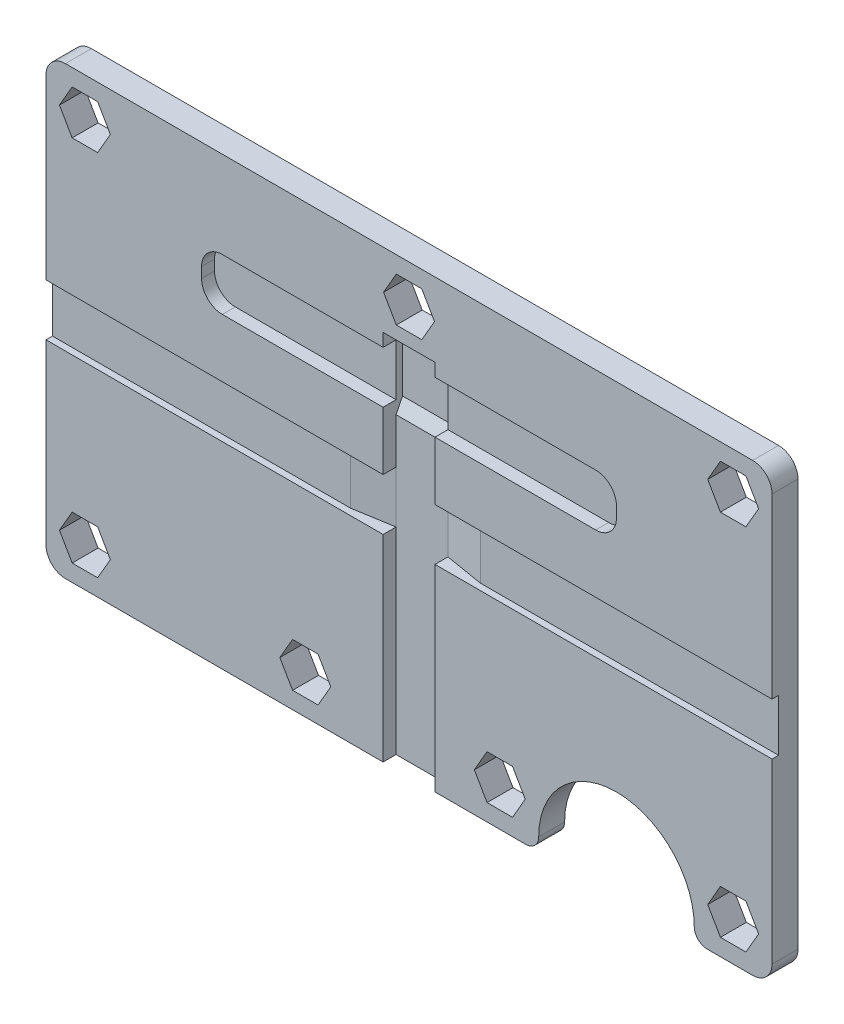
SolidWorks part; units mm, degrees
ref_plane "Front Plane" through (0, 0, 0) normal (0, 0, 1) x (1, 0, 0)
ref_plane "Top Plane" through (0, 0, 0) normal (0, 1, 0) x (1, 0, 0)
ref_plane "Right Plane" through (0, 0, 0) normal (1, 0, 0) x (0, 0, -1)
ref_plane "Plane1" through (0, 0, 1.6) normal (0, 0, 1) x (1, 0, 0)
sketch "Sketch1" plane through (0, 0, 1.6) normal (0, 0, 1) x (1, 0, 0)
  line L0 (-17.6412, 50.8492) -> (-17.6412, 1.0017)
  line L1 (-15.26, -1.3795) -> (41.0963, -1.3795)
  line L2 (63.3213, -1.3795) -> (68.8775, -1.3795)
  line L3 (71.2588, 1.0017) -> (71.2588, 50.8492)
  line L4 (68.8775, 53.2305) -> (-15.26, 53.2305)
  line L5 (26.8088, 53.1969) -> (26.8088, 50053.1969) construction
  line L6 (61.7338, 0.6891) -> (61.7338, -49999.3109) construction
  line L7 (-12.8787, 3.383) -> (37.9213, 3.383) construction
  line L15 (-9.761, 48.468) -> (-11.3199, 51.168)
  line L16 (-11.3199, 51.168) -> (-14.4376, 51.168)
  line L17 (-14.4376, 51.168) -> (-15.9964, 48.468)
  line L18 (-15.9964, 48.468) -> (-14.4376, 45.768)
  line L19 (-14.4376, 45.768) -> (-11.3199, 45.768)
  line L20 (-11.3199, 45.768) -> (-9.761, 48.468)
  line L21 (69.614, 3.383) -> (68.0551, 6.083)
  line L22 (68.0551, 6.083) -> (64.9374, 6.083)
  line L23 (64.9374, 6.083) -> (63.3786, 3.383)
  line L24 (63.3786, 3.383) -> (64.9374, 0.683)
  line L25 (64.9374, 0.683) -> (68.0551, 0.683)
  line L26 (68.0551, 0.683) -> (69.614, 3.383)
  line L27 (69.614, 48.468) -> (68.0551, 51.168)
  line L28 (68.0551, 51.168) -> (64.9374, 51.168)
  line L29 (64.9374, 51.168) -> (63.3786, 48.468)
  line L30 (63.3786, 48.468) -> (64.9374, 45.768)
  line L31 (64.9374, 45.768) -> (68.0551, 45.768)
  line L32 (68.0551, 45.768) -> (69.614, 48.468)
  line L33 (41.039, 3.383) -> (39.4801, 6.083)
  line L34 (39.4801, 6.083) -> (36.3624, 6.083)
  line L35 (36.3624, 6.083) -> (34.8036, 3.383)
  line L36 (34.8036, 3.383) -> (36.3624, 0.683)
  line L37 (36.3624, 0.683) -> (39.4801, 0.683)
  line L38 (39.4801, 0.683) -> (41.039, 3.383)
  line L39 (17.2265, 3.383) -> (15.6676, 6.083)
  line L40 (15.6676, 6.083) -> (12.5499, 6.083)
  line L41 (12.5499, 6.083) -> (10.9911, 3.383)
  line L42 (10.9911, 3.383) -> (12.5499, 0.683)
  line L43 (12.5499, 0.683) -> (15.6676, 0.683)
  line L44 (15.6676, 0.683) -> (17.2265, 3.383)
  line L45 (-9.761, 3.383) -> (-11.3199, 6.083)
  line L46 (-11.3199, 6.083) -> (-14.4376, 6.083)
  line L47 (-14.4376, 6.083) -> (-15.9964, 3.383)
  line L48 (-15.9964, 3.383) -> (-14.4376, 0.683)
  line L49 (-14.4376, 0.683) -> (-11.3199, 0.683)
  line L50 (-11.3199, 0.683) -> (-9.761, 3.383)
  line L51 (29.9265, 48.468) -> (28.3676, 51.168)
  line L52 (28.3676, 51.168) -> (25.2499, 51.168)
  line L53 (25.2499, 51.168) -> (23.6911, 48.468)
  line L54 (23.6911, 48.468) -> (25.2499, 45.768)
  line L55 (25.2499, 45.768) -> (28.3676, 45.768)
  line L56 (28.3676, 45.768) -> (29.9265, 48.468)
  circle A0 centre (-12.8787, 48.468) radius 2.3812 construction
  circle A1 centre (-12.8787, 3.383) radius 2.3813 construction
  circle A2 centre (66.4963, 3.383) radius 2.3813 construction
  circle A3 centre (66.4963, 48.468) radius 2.3813 construction
  circle A4 centre (14.1088, 3.383) radius 2.3813 construction
  circle A5 centre (37.9213, 3.383) radius 2.3813 construction
  circle A6 centre (26.8088, 48.468) radius 2.3813 construction
  arc A7 (-17.6412, 1.0017) -> (-15.26, -1.3795) centre (-15.26, 1.0017) ccw
  arc A8 (41.0963, -1.3795) -> (42.6838, 0.208) centre (41.0963, 0.208) ccw
  arc A9 (42.6838, 0.208) -> (61.7338, 0.208) centre (52.2088, 0.208) cw
  arc A10 (61.7338, 0.208) -> (63.3213, -1.3795) centre (63.3213, 0.208) ccw
  arc A11 (68.8775, -1.3795) -> (71.2588, 1.0017) centre (68.8775, 1.0017) ccw
  arc A12 (71.2588, 50.8492) -> (68.8775, 53.2305) centre (68.8775, 50.8492) ccw
  arc A13 (-15.26, 53.2305) -> (-17.6412, 50.8492) centre (-15.26, 50.8492) ccw
  circle A14 centre (-12.8787, 48.468) radius 2.7 construction
  circle A15 centre (66.4963, 3.383) radius 2.7 construction
  circle A16 centre (66.4963, 48.468) radius 2.7 construction
  circle A17 centre (37.9213, 3.383) radius 2.7 construction
  circle A18 centre (14.1088, 3.383) radius 2.7 construction
  circle A19 centre (-12.8787, 3.383) radius 2.7 construction
  circle A20 centre (26.8088, 48.468) radius 2.7 construction
  point P35 (26.8088, 53.2305)
  point P36 (12.5213, 3.383)
  dimension "D1" = 4.7625
  dimension "D2" = 4.7625
  dimension "D4" = 88.9
  dimension "D6" = 4.7625
  dimension "D13" = 1.5875
  dimension "D14" = 9.525
  dimension "D3" = 4.7625
  dimension "D5" = 54.61
  dimension "D7" = 4.7625
  dimension "D8" = 4.7625
  dimension "D9" = 4.7625
  dimension "D10" = 4.7625
  dimension "D11" = 4.7625
  dimension "D12" = 4.7625
  dimension "D15" = 19.05
  dimension "D16" = 4.7625
  dimension "D17" = 4.7625
  dimension "D18" = 3.175
  dimension "D19" = 31.75
  dimension "D20" = 5.4
  dimension "D21" = 5.4
  dimension "D22" = 5.4
  dimension "D23" = 5.4
  dimension "D24" = 5.4
  dimension "D25" = 5.4
  dimension "D26" = 5.4
extrude "Boss-Extrude1" add sketch "Sketch1" against normal blind 3.175
sketch "Sketch2" plane through (0, 0, 1.6) normal (0, 0, 1) x (1, 0, 0)
  line L0 (-17.6412, 50.8492) -> (-17.6412, 1.0017) construction
  line L1 (-17.6412, 29.1005) -> (71.2588, 29.1005)
  line L2 (-17.6412, 29.1005) -> (-17.6412, 22.7505)
  line L3 (-17.6412, 22.7505) -> (71.2588, 22.7505)
  line L4 (71.2588, 29.1005) -> (71.2588, 22.7505)
  line L5 (71.2588, 50.8492) -> (71.2588, 1.0017) construction
  point P10 (-17.6412, 25.9255)
  dimension "D1" = 6.35
extrude "Cut-Extrude1" cut sketch "Sketch2" against normal blind 0.7937
sketch "Sketch3" plane through (0, 0, 1.6) normal (0, 0, 1) x (1, 0, 0)
  line L0 (-15.26, -1.3795) -> (68.8775, -1.3795) construction
  line L1 (23.6338, 29.1005) -> (29.9838, 29.1005)
  line L2 (23.6338, 29.1005) -> (23.6338, -1.3795)
  line L3 (23.6338, -1.3795) -> (29.9838, -1.3795)
  line L4 (29.9838, 29.1005) -> (29.9838, -1.3795)
  line L5 (71.2588, 29.1005) -> (-17.6412, 29.1005) construction
  point P8 (26.8088, -1.3795)
  dimension "D1" = 6.35
extrude "Cut-Extrude2" cut sketch "Sketch3" against normal blind 1.5875
chamfer "Chamfer1" distance 4.7625 distance2 0.7937 2 edges at (23.6338, 25.9255, 0.8063) (29.9838, 25.9255, 0.8063) first distance on face at (2.9963, 25.9255, 0.8063) first distance on face at (50.6213, 25.9255, 0.8063)
sketch "Sketch4" plane through (0, 0, 1.6) normal (0, 0, 1) x (1, 0, 0)
  line L0 (29.9838, 29.1005) -> (23.6338, 29.1005) construction
  line L1 (23.6338, 44.1805) -> (29.9838, 44.1805)
  line L2 (23.6338, 44.1805) -> (23.6338, 29.1005)
  line L3 (23.6338, 29.1005) -> (29.9838, 29.1005)
  line L4 (29.9838, 44.1805) -> (29.9838, 29.1005)
  line L5 (25.2499, 45.768) -> (28.3676, 45.768) construction
  line L6 (26.8088, 44.1805) -> (26.8088, -49955.8195) construction
  point P6 (26.8088, 29.1005)
  point P7 (26.8088, 29.1005)
  point P10 (0, 0)
  point P11 (0, 0)
  point P12 (0, 0)
  point P17 (26.8088, 44.1805)
  point P18 (0, 0)
  dimension "D1" = 1.5875
extrude "Cut-Extrude3" cut sketch "Sketch4" against normal blind 1.5875
sketch "Sketch6" plane through (0, 0, 0.0125) normal (0, 0, 1) x (1, 0, 0)
  line L0 (26.8088, 44.1805) -> (26.8088, -49955.8195) construction
  line L1 (23.6338, 42.593) -> (29.9838, 42.593)
  line L2 (23.6338, 42.593) -> (23.6338, 36.243)
  line L3 (23.6338, 36.243) -> (29.9838, 36.243)
  line L4 (29.9838, 42.593) -> (29.9838, 36.243)
  line L5 (29.9838, 44.1805) -> (23.6338, 44.1805) construction
  line L6 (29.9838, 29.1005) -> (29.9838, 44.1805) construction
  line L7 (29.9838, 44.1805) -> (23.6338, 44.1805) construction
  point P8 (26.8088, 44.1805)
  point P9 (26.8088, 42.593)
  dimension "D1" = 1.5875
  dimension "D2" = 6.35
extrude "Cut-Extrude4" cut sketch "Sketch6" against normal blind 0.7937
chamfer "Chamfer2" distance 1.5875 distance2 0.7937 2 edges at (26.8088, 36.243, 0.0125) (26.8088, 42.593, 0.0125) first distance on face at (26.8088, 21.6786, 0.0125) first distance on face at (26.8088, 43.3867, 0.0125)
sketch "Sketch7" plane through (0, 0, 1.6) normal (0, 0, 1) x (1, 0, 0)
  line L0 (29.9838, 42.593) -> (23.6338, 42.593) construction
  line L1 (49.6688, 42.593) -> (3.9488, 42.593)
  line L2 (52.2088, 40.053) -> (52.2088, 38.783)
  line L3 (49.6688, 36.243) -> (3.9488, 36.243)
  line L4 (1.4088, 40.053) -> (1.4088, 38.783)
  line L7 (23.6338, 36.243) -> (29.9838, 36.243) construction
  arc A0 (52.2088, 40.053) -> (49.6688, 42.593) centre (49.6688, 40.053) ccw
  arc A1 (49.6688, 36.243) -> (52.2088, 38.783) centre (49.6688, 38.783) ccw
  arc A2 (1.4088, 38.783) -> (3.9488, 36.243) centre (3.9488, 38.783) ccw
  arc A3 (1.4088, 40.053) -> (3.9488, 42.593) centre (3.9488, 40.053) cw
  point P8 (26.8088, 42.593)
  point P9 (26.8088, 42.593)
  point P14 (52.2088, 36.243)
  point P17 (1.4088, 36.243)
  dimension "D2" = 2.54
  dimension "D1" = 50.8
extrude "Cut-Extrude5" cut sketch "Sketch7" against normal blind 1.5875
